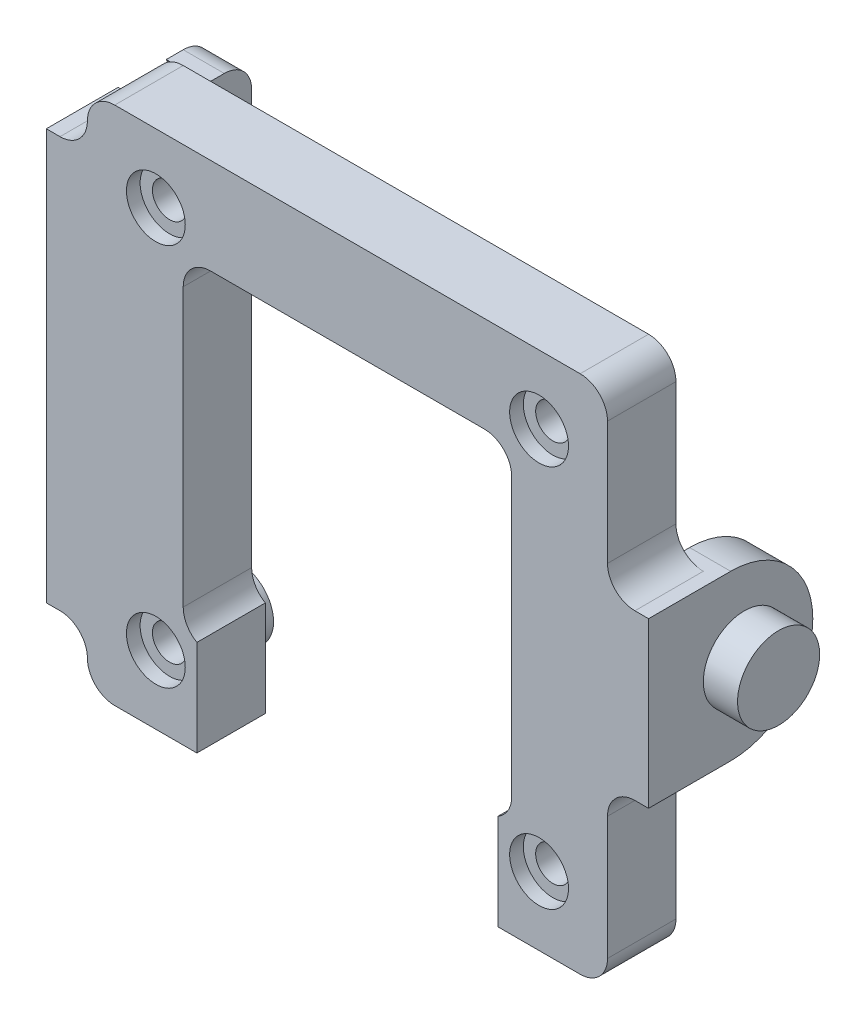
SolidWorks part; units mm, degrees
ref_plane "前视基准面" through (0, 0, 0) normal (0, 0, 1) x (1, 0, 0)
ref_plane "上视基准面" through (0, 0, 0) normal (0, 1, 0) x (1, 0, 0)
ref_plane "右视基准面" through (0, 0, 0) normal (1, 0, 0) x (0, 0, -1)
sketch "草图1" plane through (0, 0, 0) normal (0, 0, 1) x (1, 0, 0)
  line L0 (-14, 14) -> (14, 14) construction
  line L1 (19, -19) -> (12, -19)
  line L2 (19, -19) -> (19, 19)
  line L3 (19, 19) -> (-19, 19)
  line L4 (-19, -19) -> (-19, 19)
  line L5 (19, -19) -> (-19, 19) construction
  line L6 (19, 19) -> (-19, -19) construction
  line L7 (14, 14) -> (14, -14) construction
  line L8 (14, -14) -> (-14, -14) construction
  line L9 (-14, -14) -> (-14, 14) construction
  line L12 (12, -12) -> (12, 12)
  line L13 (12, 12) -> (-12, 12)
  line L14 (-12, -12) -> (-12, 12)
  line L15 (12, -12) -> (-12, 12) construction
  line L16 (12, 12) -> (-12, -12) construction
  line L18 (-12, -19) -> (-19, -19)
  line L19 (-12, -12) -> (-11, -12)
  line L20 (-11, -12) -> (-11, -19)
  line L21 (-11, -19) -> (-12, -19)
  line L22 (12, -12) -> (11, -12)
  line L23 (11, -12) -> (11, -19)
  line L24 (11, -19) -> (12, -19)
  circle A0 centre (-14, 14) radius 1 construction
  circle A1 centre (-14, -14) radius 1 construction
  circle A2 centre (14, -14) radius 1 construction
  circle A3 centre (14, 14) radius 1 construction
  point P0 (0, 0)
  point P14 (0, 0)
  dimension "D4" = 2
  dimension "D1" = 38
  dimension "D2" = 38
  dimension "D3" = 28
  dimension "D5" = 24
  dimension "D6" = 24
  dimension "D7" = 1
extrude "凸台-拉伸1" add sketch "草图1" against normal blind 5
sketch "草图6" plane through (0, 0, 0) normal (0, 0, 1) x (1, 0, 0)
  line L0 (-14, 14) -> (14, 14) construction
  line L5 (14, 14) -> (14, -14) construction
  line L6 (14, -14) -> (-14, -14) construction
  line L7 (-14, -14) -> (-14, 14) construction
  line L8 (-14, 14) -> (14, -14) construction
  line L9 (14, 14) -> (-14, -14) construction
  circle A0 centre (-14, 14) radius 2.5
  circle A1 centre (-14, -14) radius 2.5
  circle A2 centre (14, -14) radius 2.5
  circle A3 centre (14, 14) radius 2.5
  dimension "D4" = 5
  dimension "D1" = 28
  dimension "D2" = 28
extrude "凸台-拉伸5" add sketch "草图6" against normal blind 1.1 from surface starting at face at (0, -5.1667, -5)
hole_wizard "孔1" positions "草图2" profile "草图3" legacy end condition through all
sketch "草图2" plane through (0, 0, 0) normal (0, 0, 1) x (1, 0, 0)
  line L1 (14, -14) -> (-14, -14)
  line L2 (14, -14) -> (14, 14)
  line L3 (14, 14) -> (-14, 14)
  line L4 (-14, -14) -> (-14, 14)
  line L5 (14, -14) -> (-14, 14) construction
  line L6 (14, 14) -> (-14, -14) construction
  point P1 (-14, 14)
  point P148 (14, -14)
  point P149 (14, 14)
  point P150 (-14, -14)
  point P180 (0, 0)
  point P183 (0, 0)
  point P185 (0.0083, -0.0481)
  point P189 (0, 0)
  dimension "D1" = 28
  dimension "D2" = 28
sketch "草图3" plane through (-14, 14, 0) normal (1, 0, 0) x (0, -1, 0)
  line L0 (0, 0) -> (0, 6.1)
  line L1 (0, 6.1) -> (1.25, 6.1)
  line L2 (1.25, 6.1) -> (1.25, 1)
  line L3 (1.25, 1) -> (2.15, 1)
  line L4 (2.15, 1) -> (2.15, 0)
  line L5 (2.15, 0) -> (0, 0)
  line L6 (0, 110) -> (0, -10) construction
  dimension "直径" = 2.5
  dimension "深度" = 6.1
  dimension "柱坑直径" = 4.3
  dimension "柱坑深度" = 1
fillet "圆角1" radius 2 8 edges at (19, -19, -2.5) (19, 19, -2.5) (-19, 19, -2.5) (12, 12, -2.5) (-19, -19, -2.5) (12, -12, -2.5) (-12, -12, -2.5) (-12, 12, -2.5)
sketch "草图5" plane through (-19, 0, 0) normal (-1, 0, 0) x (0, 0, 1)
  line L0 (0, 17) -> (0, -17) construction
  line L1 (-12, -15) -> (0, -15)
  line L2 (-12, -15) -> (-12, 15)
  line L3 (-12, 15) -> (0, 15)
  line L4 (0, -15) -> (0, 15)
  line L5 (-12, -15) -> (0, 15) construction
  line L6 (-12, 15) -> (0, -15) construction
  line L7 (0, 0) -> (-6, 0) construction
  point P0 (-6, 0)
  dimension "D1" = 30
  dimension "D2" = 12
extrude "凸台-拉伸3" add sketch "草图5" along normal blind 3
sketch "草图9" plane through (-22, 0, -24) normal (1, 0, 0) x (0, 0, -1)
  line L0 (-17, 0) -> (-17, -14.05) construction
  line L1 (-18.997, -14.1591) -> (-19.65, -2.2091)
  line L2 (-14.35, -2.2091) -> (-15.003, -14.1591)
  line L3 (-12, 0) -> (-17, 0) construction
  line L4 (-12, 15) -> (-12, -15) construction
  line L5 (-24, -15) -> (-24, 15) construction
  arc A0 (-14.35, -2.2091) -> (-19.65, -2.2091) centre (-17, 0) ccw
  arc A1 (-18.997, -14.1591) -> (-15.003, -14.1591) centre (-17, -14.05) ccw
  point P2 (0, 0)
  dimension "D1" = 6.9
  dimension "D2" = 4
  dimension "D3" = 19.5
  dimension "D4" = 5.3
  dimension "D5" = 7
extrude "切除-拉伸1" cut sketch "草图9" along normal blind 1.4
mirror "镜向2" about plane through (0, 0, 0) normal (0, 1, 0) of "切除-拉伸1"
sketch "草图10" plane through (19, 0, 0) normal (1, 0, 0) x (0, 0, -1)
  line L0 (0, -17) -> (0, 17) construction
  line L1 (0, 6) -> (12, 6)
  line L2 (0, 6) -> (0, -6)
  line L3 (0, -6) -> (12, -6)
  line L4 (12, 6) -> (12, -6)
  line L5 (12, 15) -> (12, -15) construction
  line L6 (0, 0) -> (12, 0) construction
  dimension "D1" = 12
extrude "凸台-拉伸6" add sketch "草图10" along normal blind 3
sketch "草图11" plane through (22, 0, 0) normal (1, 0, 0) x (0, 0, -1)
  line L0 (0, 0) -> (7, 0) construction
  line L4 (0, 6) -> (0, -6)
  line L5 (0, -6) -> (12, -6)
  line L6 (12, -6) -> (12, 6)
  line L7 (12, 6) -> (0, 6)
  line L8 (0, 6) -> (0, -6) construction
  circle A0 centre (7, 0) radius 3
  dimension "D3" = 6
  dimension "D2" = 7
  dimension "D1" = 0
extrude "凸台-拉伸7" add sketch "草图11" along normal blind 2.5
fillet "圆角2" 2 edges at (20.5, 6, -12) (20.5, -6, -12) type full round first side face at (20.2, 6, -5.8) second side face at (20.2, -6, -5.8) middle face at (20.5, 0, -12)
fillet "圆角4" radius 2 4 edges at (19, -6, -2.5) (19, 6, -2.5) (-19, 15, -2.5) (-19, -15, -2.5)
fillet "圆角5" radius 2 2 edges at (-20.5, 15, -12) (-20.5, -15, -12)
